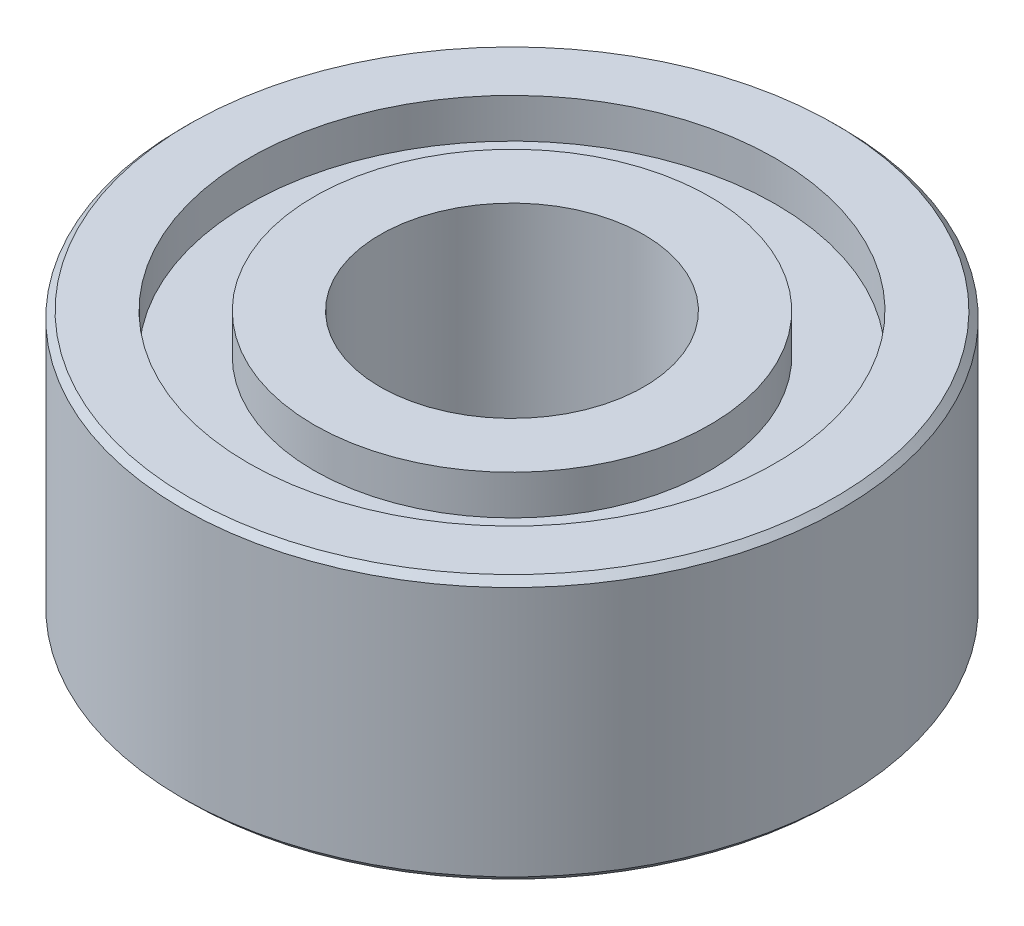
SolidWorks part; units mm, degrees
ref_plane "Front Plane" through (0, 0, 0) normal (0, 0, 1) x (1, 0, 0)
ref_plane "Top Plane" through (0, 0, 0) normal (0, 1, 0) x (1, 0, 0)
ref_plane "Right Plane" through (0, 0, 0) normal (1, 0, 0) x (0, 0, -1)
sketch "Sketch1" plane through (0, 0, 0) normal (0, 1, 0) x (1, 0, 0)
  circle A0 centre (0, 0) radius 2
  circle A1 centre (0, 0) radius 5
  dimension "D1" = 4
  dimension "D2" = 10
extrude "Boss-Extrude1" add sketch "Sketch1" along normal blind 2 and the other way blind 2
sketch "Sketch2" plane through (0, 2, 0) normal (0, 1, 0) x (1, 0, 0)
  circle A0 centre (0, 0) radius 3
  circle A1 centre (0, 0) radius 4
  dimension "D1" = 8
  dimension "D2" = 6
extrude "Cut-Extrude1" cut sketch "Sketch2" against normal blind 0.6
mirror "Mirror2" about plane through (0, 0, 0) normal (0, 1, 0) of "Cut-Extrude1"
chamfer "Chamfer1" distance 0.1 angle 45 2 edges at (0, -2, 5) (0, 2, 5)
